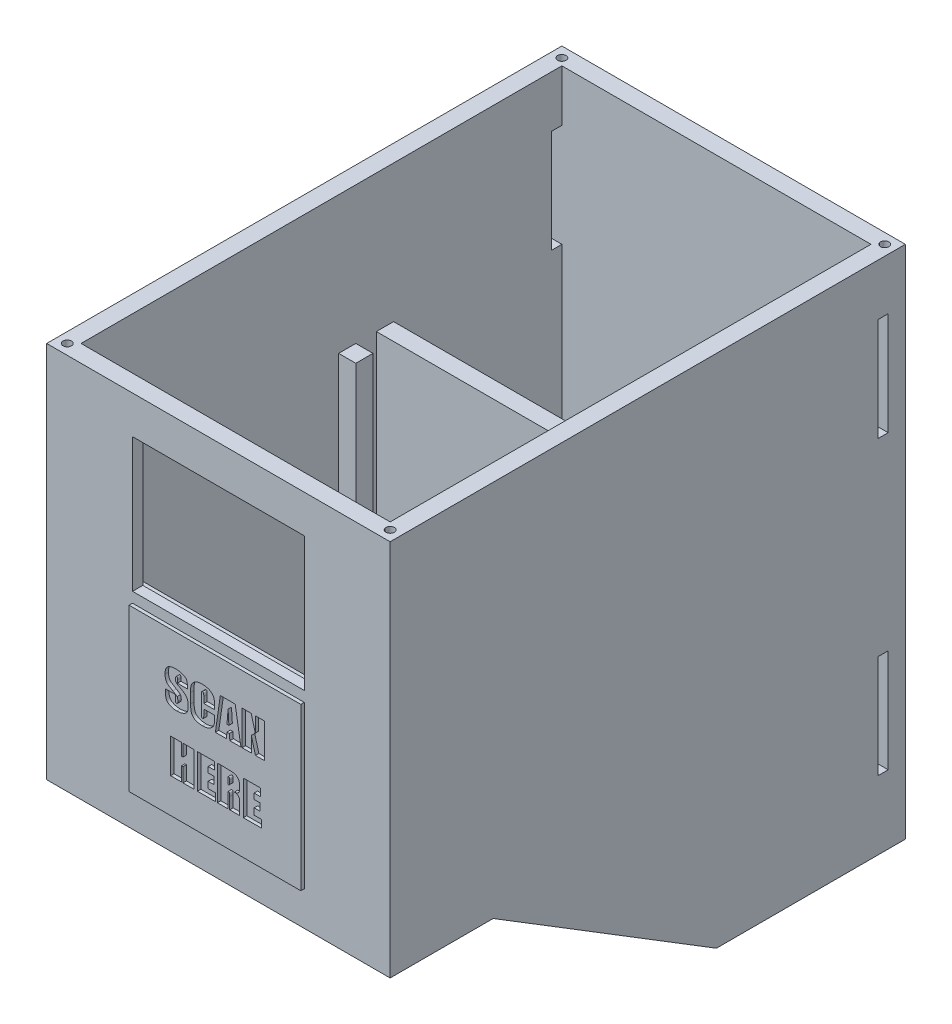
SolidWorks part; units mm, degrees
ref_plane "Front Plane" through (0, 0, 0) normal (0, 0, 1) x (1, 0, 0)
ref_plane "Top Plane" through (0, 0, 0) normal (0, 1, 0) x (1, 0, 0)
ref_plane "Right Plane" through (0, 0, 0) normal (1, 0, 0) x (0, 0, -1)
sketch "Sketch1" plane through (0, 0, 0) normal (0, 1, 0) x (1, 0, 0)
  line L1 (-50, -75) -> (50, -75)
  line L2 (-50, -75) -> (-50, 75)
  line L3 (-50, 75) -> (50, 75)
  line L4 (50, -75) -> (50, 75)
  line L5 (-50, -75) -> (50, 75) construction
  line L6 (-50, 75) -> (50, -75) construction
  point P0 (0, 0)
  dimension "D1" = 100
  dimension "D2" = 150
extrude "Boss-Extrude1" add sketch "Sketch1" along normal blind 150
sketch "Sketch13" plane through (50, 0, 0) normal (1, 0, 0) x (0, 0, -1)
  line L0 (-45, 40) -> (20, 0)
  line L1 (-75, 0) -> (-45, 0)
  line L2 (-75, 0) -> (-75, 40)
  line L3 (-75, 40) -> (-45, 40)
  line L5 (-75, 0) -> (75, 0) construction
  line L8 (-45, 0) -> (20, 0)
  dimension "D1" = 30
  dimension "D2" = 40
  dimension "D3" = 55
extrude "Cut-Extrude7" cut sketch "Sketch13" against normal up to next
shell "Shell1" thickness 5 removed face at (0, 150, 0)
sketch "Sketch3" plane through (0, 0, 0) normal (0, -1, 0) x (1, 0, 0)
  line L1 (50, 45) -> (50, 75) construction
  circle A0 centre (0, 60) radius 4
  circle A1 centre (-5, 50) radius 1.5
  circle A2 centre (5, 50) radius 1.5
  dimension "D3" = 8
  dimension "D4" = 3
  dimension "D5" = 10
  dimension "D7" = 10
  dimension "D8" = 5
  dimension "D1" = 60
  dimension "D2" = 50
extrude "Cut-Extrude2" cut sketch "Sketch3" against normal up to next
sketch "Sketch5" plane through (0, 0, 75) normal (0, 0, 1) x (1, 0, 0)
  line L0 (50, 150) -> (50, 40) construction
  line L1 (-25, 50) -> (25, 50)
  line L2 (-25, 50) -> (-25, 97)
  line L3 (-25, 97) -> (25, 97)
  line L4 (25, 50) -> (25, 97)
  line L5 (-25, 50) -> (25, 97) construction
  line L6 (-25, 97) -> (25, 50) construction
  line L7 (-50, 150) -> (50, 150) construction
  point P0 (0, 73.5)
  dimension "D1" = 50
  dimension "D2" = 47
  dimension "D3" = 50
  dimension "D4" = 76.5
extrude "Boss-Extrude3" add sketch "Sketch5" along normal blind 1
sketch "Sketch8" plane through (0, 0, 75) normal (0, 0, 1) x (1, 0, 0)
  line L0 (-50, 150) -> (-50, 40) construction
  line L1 (-25, 100) -> (25, 100)
  line L2 (-25, 100) -> (-25, 139)
  line L3 (-25, 139) -> (25, 139)
  line L4 (25, 100) -> (25, 139)
  line L5 (-25, 100) -> (25, 139) construction
  line L6 (-25, 139) -> (25, 100) construction
  line L7 (-50, 150) -> (50, 150) construction
  point P0 (0, 119.5)
  dimension "D1" = 50
  dimension "D2" = 39
  dimension "D3" = 50
  dimension "D4" = 50
extrude "Cut-Extrude3" cut sketch "Sketch8" against normal up to next
sketch "Sketch18" plane through (0, 0, 70) normal (0, 0, -1) x (-1, 0, 0)
  line L0 (-25, 139) -> (25, 139) construction
  line L1 (30, 99) -> (-26, 99)
  line L2 (30, 99) -> (30, 140)
  line L3 (30, 140) -> (-26, 140)
  line L4 (-26, 99) -> (-26, 140)
  line L6 (-25, 100) -> (-25, 139) construction
  line L7 (25, 139) -> (25, 100) construction
  dimension "D1" = 1
  dimension "D2" = 41
  dimension "D3" = 1
  dimension "D4" = 5
extrude "Cut-Extrude9" cut sketch "Sketch18" against normal blind 2
sketch "Sketch20" plane through (0, 0, 76) normal (0, 0, 1) x (1, 0, 0)
  line L0 (25, 97) -> (-25, 97) construction
  line L1 (-23, 96) -> (23, 96)
  line L2 (-23, 96) -> (-23, 51)
  line L3 (-23, 51) -> (23, 51)
  line L4 (23, 96) -> (23, 51)
  line L5 (-25, 50) -> (25, 50) construction
  line L6 (25, 50) -> (25, 97) construction
  line L7 (-25, 97) -> (-25, 50) construction
  dimension "D1" = 1
  dimension "D2" = 1
  dimension "D3" = 2
  dimension "D4" = 2
extrude "Cut-Extrude10" cut sketch "Sketch20" against normal blind 15 from offset 4 offset against normal yes
sketch "Sketch21" plane through (0, 45, 0) normal (0, 1, 0) x (1, 0, 0)
  line L1 (9, -52.5) -> (-9, -52.5)
  line L2 (9, -52.5) -> (9, -37.5)
  line L3 (9, -37.5) -> (-9, -37.5)
  line L4 (-9, -52.5) -> (-9, -37.5)
  circle A0 centre (5, -50) radius 1.5 construction
  circle A1 centre (-5, -50) radius 1.5 construction
  dimension "D3" = 4
  dimension "D1" = 4
  dimension "D2" = 2.5
  dimension "D4" = 15
extrude "Cut-Extrude11" cut sketch "Sketch21" against normal blind 2.5
sketch "Sketch22" plane through (-45, 0, 0) normal (1, 0, 0) x (0, 0, -1)
  line L0 (70, 150) -> (-70, 150) construction
  line L5 (70, 150) -> (70, 5) construction
  line L7 (-43.5848, 45) -> (21.4152, 5) construction
  line L8 (10, 150) -> (10, 12.0247)
  line L11 (10, 150) -> (5, 150)
  line L14 (5, 150) -> (5, 15.1017)
  line L15 (5, 15.1017) -> (10, 12.0247)
  dimension "D1" = 60
  dimension "D3" = 5
extrude "Boss-Extrude6" add sketch "Sketch22" along normal blind 5
mirror "Mirror2" about plane through (0, 0, 0) normal (1, 0, 0) of "Boss-Extrude6"
sketch "Sketch23" plane through (-45, 0, 0) normal (1, 0, 0) x (0, 0, -1)
  line L0 (16, 150) -> (21, 150)
  line L1 (70, 150) -> (10, 150) construction
  line L3 (21, 150) -> (21, 5.2555)
  line L4 (21, 5.2555) -> (16, 8.3324)
  line L6 (10, 12.0247) -> (10, 150) construction
  line L7 (16, 150) -> (16, 8.3324)
  line L8 (10, 12.0247) -> (21.4152, 5) construction
  dimension "D1" = 6
  dimension "D2" = 5
extrude "Boss-Extrude7" add sketch "Sketch23" along normal up to next
sketch "Sketch24" plane through (-45, 0, 0) normal (1, 0, 0) x (0, 0, -1)
  line L0 (70, 150) -> (70, 5) construction
  line L1 (70, 135) -> (67, 135)
  line L2 (70, 135) -> (70, 105)
  line L3 (70, 105) -> (67, 105)
  line L4 (67, 135) -> (67, 105)
  line L5 (70, 150) -> (21, 150) construction
  line L6 (70, 5) -> (21.4152, 5) construction
  line L7 (70, 20) -> (67, 20)
  line L8 (70, 20) -> (70, 50)
  line L9 (70, 50) -> (67, 50)
  line L10 (67, 20) -> (67, 50)
  dimension "D1" = 15
  dimension "D2" = 30
  dimension "D3" = 3
  dimension "D4" = 15
extrude "Cut-Extrude12" cut sketch "Sketch24" against normal through all both and the other way through all
sketch "Sketch28" plane through (0, 0, 76) normal (0, 0, 1) x (1, 0, 0)
  line L0 (-25, 73.5) -> (25, 73.5) construction
  line L1 (-25, 97) -> (-25, 50) construction
  line L2 (25, 50) -> (25, 97) construction
  line L3 (-25, 77.511) -> (25, 77.511) construction
  text T0 "SCAN\r\nHERE" font "Impact" height 10
extrude "Cut-Extrude14" cut sketch "Sketch28" against normal blind 1
sketch "Sketch30" plane through (0, 0, -75) normal (0, 0, -1) x (-1, 0, 0)
  text T0 "IBE VAN DE VEIRE\r\nSTEF GIELEN" font "Comic Sans MS" height 5
extrude "Cut-Extrude16" cut sketch "Sketch30" against normal blind 1
sketch "Sketch32" plane through (0, 150, 0) normal (0, 1, 0) x (1, 0, 0)
  line L0 (-50, 75) -> (-50, -75) construction
  line L1 (50, 75) -> (-50, 75) construction
  line L2 (-50, -75) -> (50, -75) construction
  line L3 (50, -75) -> (50, 75) construction
  circle A0 centre (-47, 72) radius 1.225
  circle A1 centre (-47, -72) radius 1.225
  circle A2 centre (47, -72) radius 1.225
  circle A3 centre (47, 72) radius 1.225
  dimension "D1" = 2.45
  dimension "D2" = 3
  dimension "D3" = 3
  dimension "D4" = 2.45
  dimension "D5" = 3
  dimension "D6" = 3
  dimension "D7" = 2.45
  dimension "D8" = 3
  dimension "D9" = 3
  dimension "D10" = 2.45
  dimension "D11" = 3
  dimension "D12" = 3
extrude "Cut-Extrude17" cut sketch "Sketch32" against normal blind 20
sketch "Sketch33" plane through (0, 150, 0) normal (0, 1, 0) x (1, 0, 0)
  line L1 (-45, 5) -> (45, 5)
  line L2 (-45, 5) -> (-45, 21)
  line L3 (-45, 21) -> (45, 21)
  line L4 (45, 5) -> (45, 21)
extrude "Cut-Extrude18" cut sketch "Sketch33" against normal blind 40
sketch "Sketch34" plane through (0, 150, 0) normal (0, 1, 0) x (1, 0, 0)
  line L0 (50, 75) -> (-50, 75) construction
  line L1 (-45, 75) -> (50, 75)
  line L2 (-45, 75) -> (-45, -75)
  line L3 (-45, -75) -> (50, -75)
  line L4 (50, 75) -> (50, -75)
sketch "Sketch35" plane through (-50, 0, 0) normal (-1, 0, 0) x (0, 0, 1)
  line L0 (-20, 0) -> (45, 40)
  line L1 (45, 40) -> (42.3795, 44.2583)
  line L2 (42.3795, 44.2583) -> (-22.6205, 4.2583)
  line L3 (-22.6205, 4.2583) -> (-20, 0)
  dimension "D1" = 5
